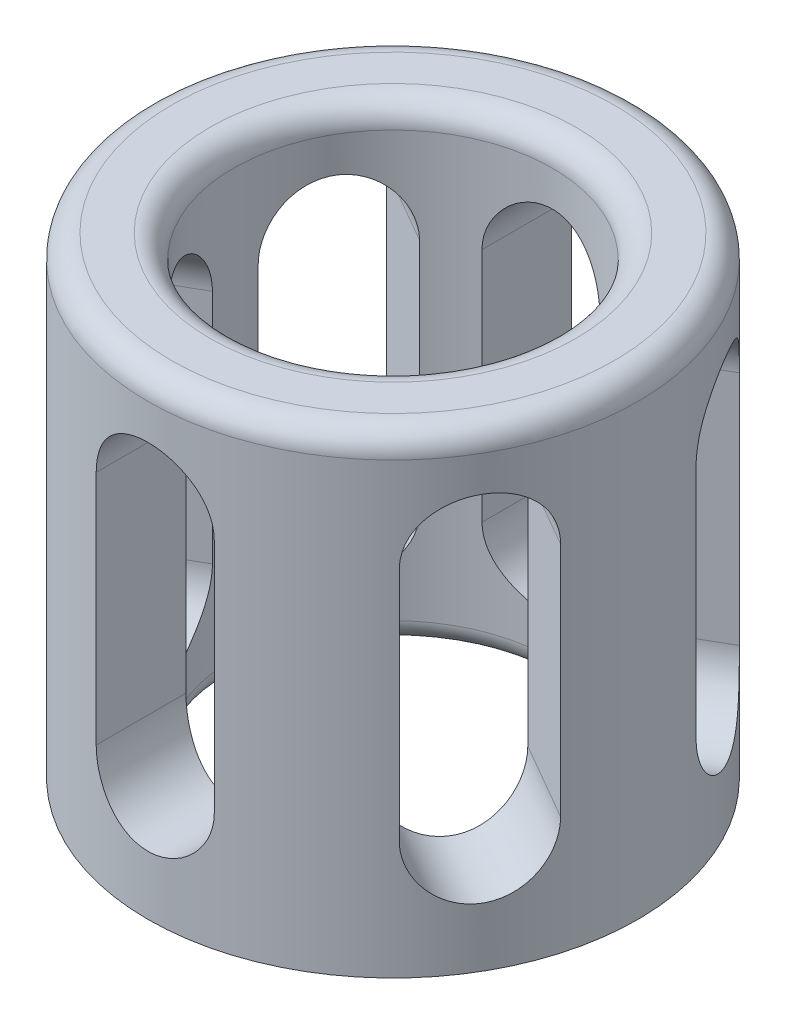
SolidWorks part; units mm, degrees
ref_plane "Front" through (0, 0, 0) normal (0, 0, 1) x (1, 0, 0)
ref_plane "Top" through (0, 0, 0) normal (0, 1, 0) x (1, 0, 0)
ref_plane "Right" through (0, 0, 0) normal (1, 0, 0) x (0, 0, -1)
sketch "Sketch1" plane through (0, 0, 0) normal (0, 1, 0) x (1, 0, 0)
  circle A0 centre (0, 0) radius 20.75
  circle A1 centre (0, 0) radius 13.5
  dimension "D1" = 41.5
  dimension "D2" = 27
extrude "Boss-Extrude1" add sketch "Sketch1" along normal blind 40
ref_plane "Plane1" through (0, 0, 20.75) normal (0, 0, 1) x (1, 0, 0)
sketch "Sketch2" plane through (0, 0, 20.75) normal (0, 0, 1) x (1, 0, 0)
  line L0 (0, 40) -> (0, 0) construction
  line L1 (20.75, 40) -> (-20.75, 40) construction
  line L2 (-20.75, 0) -> (20.75, 0) construction
  line L3 (-5, 20) -> (5, 20) construction
  line L4 (-5, 30) -> (5, 30)
  line L5 (-5, 30) -> (-5, 10)
  line L6 (-5, 10) -> (5, 10)
  line L7 (5, 30) -> (5, 10)
  line L8 (-5, 30) -> (5, 10) construction
  line L9 (-5, 10) -> (5, 30) construction
  arc A0 (-5, 30) -> (5, 30) centre (0, 30) cw
  arc A1 (-5, 10) -> (5, 10) centre (0, 10) ccw
  point P6 (0, 20)
  dimension "D1" = 10
  dimension "D2" = 20
extrude "Cut-Extrude1" cut sketch "Sketch2" against normal blind 20 contours L6 A1 | L7 L4 L5 L6 | A0 L4 region at (0, 32.1221, 20.75) region at (0, 20, 20.75) region at (0, 7.8779, 20.75)
pattern_circular "CirPattern1" count 6 over 360 about axis through (0, 40, 0) along (0, -1, 0) of "Cut-Extrude1"
fillet "Fillet1" radius 2 3 edges at (0, 40, 20.75) (0, 0, 13.5) (0, 40, 13.5)
